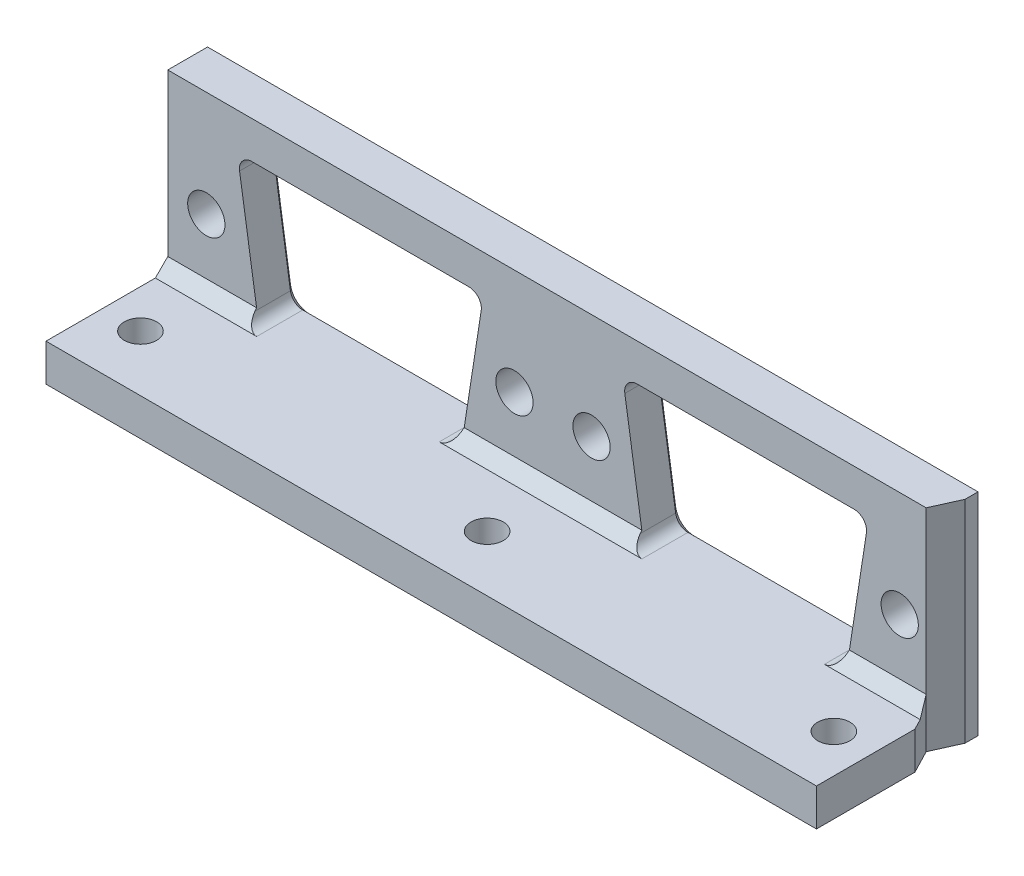
SolidWorks part; units mm, degrees
ref_plane "Front Plane" through (0, 0, 0) normal (0, 0, 1) x (1, 0, 0)
ref_plane "Top Plane" through (0, 0, 0) normal (0, 1, 0) x (1, 0, 0)
ref_plane "Right Plane" through (0, 0, 0) normal (1, 0, 0) x (0, 0, -1)
sketch "Sketch1" plane through (0, 0, 0) normal (0, 0, 1) x (1, 0, 0)
  line L0 (-31, -3) -> (31, -3)
  line L1 (0, -16.7207) -> (0, 18.3534) construction
  line L2 (7.3, 0) -> (23.7, 0)
  line L3 (5.6, 11) -> (25.4, 11)
  line L4 (-7.3, 0) -> (-23.7, 0)
  line L5 (-5.6, 11) -> (-25.4, 11)
  line L6 (-23.7, 0) -> (-25.4, 11)
  line L7 (-5.6, 11) -> (-7.3, 0)
  line L8 (5.6, 11) -> (7.3, 0)
  line L9 (25.4, 11) -> (23.7, 0)
  line L10 (-31, 14) -> (31, 14)
  line L11 (-31, 14) -> (-31, -3)
  line L12 (31, 14) -> (31, -3)
  line L13 (39.5729, 5.5) -> (-35.811, 5.5) construction
  circle A0 centre (27.9, 5.5) radius 1.5
  circle A1 centre (3.1, 5.5) radius 1.5
  circle A2 centre (-3.1, 5.5) radius 1.5
  circle A3 centre (-27.9, 5.5) radius 1.5
  point P2 (0, -3)
  point P18 (15.5, 0)
  point P19 (15.5, 11)
  point P20 (-15.5, 11)
  point P21 (-15.5, 0)
  dimension "D12" = 3
  dimension "D1" = 62
  dimension "D2" = 3
  dimension "D3" = 11
  dimension "D4" = 17
  dimension "D5" = 16.4
  dimension "D6" = 19.8
  dimension "D7" = 19.8
  dimension "D8" = 16.4
  dimension "D9" = 5.6
  dimension "D11" = 5.6
  dimension "D10" = 5.5
  dimension "D13" = 24.8
  dimension "D14" = 24.8
  dimension "D15" = 3.1
  dimension "D16" = 3.1
extrude "Boss-Extrude1" add sketch "Sketch1" along normal blind 3.2
sketch "Sketch2" plane through (0, -3, 0) normal (0, -1, 0) x (1, 0, 0)
  line L0 (-34.3715, 8.5) -> (38.2248, 8.5) construction
  line L1 (-31, 0) -> (31, 0)
  line L2 (-31, 0) -> (-31, 13)
  line L3 (-31, 13) -> (31, 13)
  line L4 (31, 0) -> (31, 13)
  circle A0 centre (0, 8.5) radius 1.3
  circle A1 centre (-27.9, 8.5) radius 1.3
  circle A2 centre (27.9, 8.5) radius 1.3
  dimension "D2" = 2.6
  dimension "D1" = 13
  dimension "D3" = 27.9
  dimension "D4" = 27.9
  dimension "D5" = 62
  dimension "D6" = 8.5
extrude "Boss-Extrude2" add sketch "Sketch2" against normal blind 3
fillet "Fillet1" radius 1 8 edges at (-25.4, 11, 1.6) (-7.3, 0, 1.6) (-23.7, 0, 1.6) (-5.6, 11, 1.6) (5.6, 11, 1.6) (7.3, 0, 1.6) (23.7, 0, 1.6) (25.4, 11, 1.6)
chamfer "Chamfer2" distance 0.5 angle 45 16 edges at (-23.4935, 0.2408, 0) (-15.5, 0, 0) (-7.5065, 0.2408, 0) (-6.4736, 5.3473, 0) (-6.0072, 10.6509, 0) (-24.5264, 5.3473, 0) (-24.9928, 10.6509, 0) (-15.5, 11, 0) (24.5264, 5.3473, 0) (15.5, 11, 0) (24.9928, 10.6509, 0) (6.0072, 10.6509, 0) (23.4935, 0.2408, 0) (6.4736, 5.3473, 0) (7.5065, 0.2408, 0) (15.5, 0, 0)
chamfer "Chamfer3" distance 1 angle 45 3 edges at (-26.9213, 0, 3.2) (26.9213, 0, 3.2) (0, 0, 3.2)
sketch "Sketch3" plane through (0, 14, 0) normal (0, 1, 0) x (1, 0, 0)
  line L0 (31, -1.0368) -> (30.029, -3.2)
  line L2 (23.8545, -3.2) -> (31, -3.2) construction
  line L3 (30.029, -3.2) -> (31, -5.0758)
  line L4 (31, -4.2) -> (31, -13) construction
  line L5 (31, -5.0758) -> (31, -1.0368)
  line L6 (31, -3.2) -> (31, 0) construction
  point P2 (31, -1.0368)
  point P6 (0, 0)
extrude "Cut-Extrude1" cut sketch "Sketch3" against normal through all
equation "\"D9@Sketch1\"= (31-19.8)/2"
equation "\"D15@Sketch1\"=(31-24.8)/2"
equation "\"D3@Sketch2\"=31 - (31-24.8)/2"
